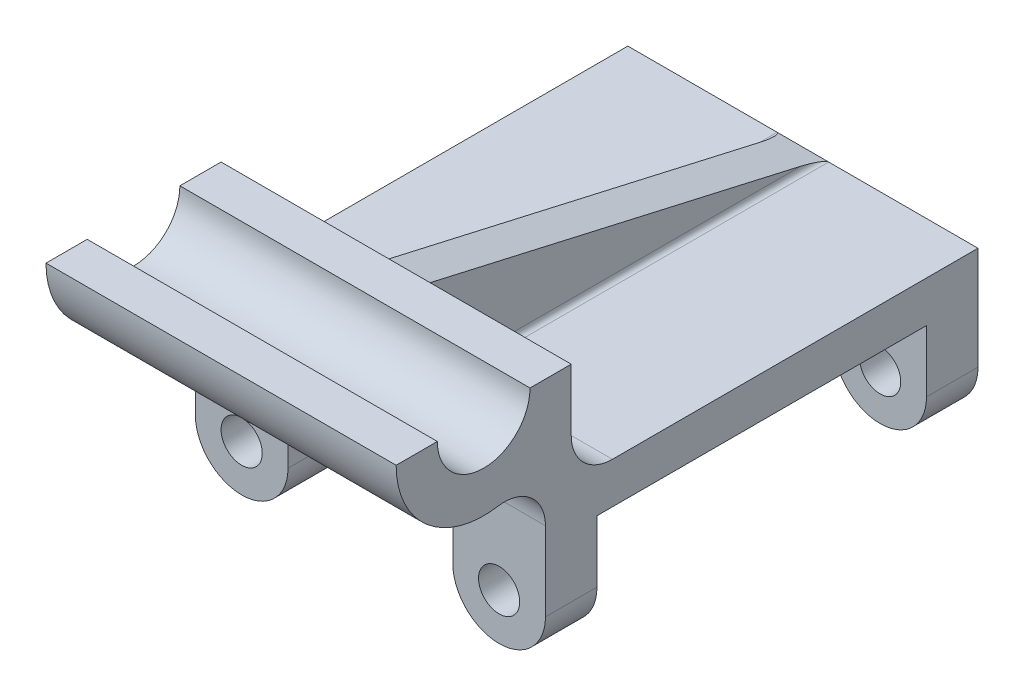
SolidWorks part; units mm, degrees
ref_plane "Front Plane" through (0, 0, 0) normal (0, 0, 1) x (1, 0, 0)
ref_plane "Top Plane" through (0, 0, 0) normal (0, 1, 0) x (1, 0, 0)
ref_plane "Right Plane" through (0, 0, 0) normal (1, 0, 0) x (0, 0, -1)
sketch "Sketch2" plane through (0, 0, 0) normal (1, 0, 0) x (0, 0, -1)
  line L0 (0, 0) -> (133.35, 0)
  line L1 (133.35, 0) -> (133.35, 12.7)
  line L2 (133.35, 12.7) -> (20.6375, 12.7)
  line L7 (0, 0) -> (0, 60.5111) construction
  line L8 (7.9375, 25.4) -> (7.9375, 44.45)
  line L9 (7.9375, 44.45) -> (-4.7625, 44.45)
  line L10 (-33.3375, 44.45) -> (-46.0375, 44.45)
  line L11 (0, 5.2738) -> (0, 0)
  line L12 (-37.3298, 44.45) -> (7.9375, 44.45) construction
  arc A2 (-33.3375, 44.45) -> (-4.7625, 44.45) centre (-19.05, 44.45) ccw
  arc A3 (20.6375, 12.7) -> (7.9375, 25.4) centre (20.6375, 25.4) cw
  arc A4 (-46.0375, 44.45) -> (-14.732, 17.8102) centre (-19.05, 44.45) ccw
  arc A5 (-14.732, 17.8102) -> (0, 5.2738) centre (-12.7, 5.2738) cw
  point P16 (0, 0)
  point P17 (0, 0)
  point P18 (0, 0)
  point P20 (0, 0)
  point P21 (0, 0)
  point P22 (0, 5.2738)
  dimension "D3" = 28.575
  dimension "D7" = 12.7
  dimension "D8" = 44.45
  dimension "D5" = 12.7
  dimension "D6" = 26.9875
  dimension "D1" = 133.35
  dimension "D2" = 12.7
  dimension "D4" = 19.05
  dimension "D9" = 12.7
extrude "Boss-Extrude1" add sketch "Sketch2" along normal mid plane 107.95
sketch "Sketch3" plane through (0, 0, 0) normal (1, 0, 0) x (0, 0, -1)
  line L0 (7.9375, 41.275) -> (133.35, 12.7)
  point P2 (0, 0)
  point P3 (0, 0)
  point P4 (0, 0)
  point P6 (0, 0)
  point P7 (7.9375, 44.45)
  dimension "D1" = 3.175
rib "Rib1" sketch "Sketch3" sketch "Sketch3" thickness 12.7 extrusion direction parallel to sketch draft on no parameters "D1"=12.7
sketch "Sketch4" plane through (0, 0, -133.35) normal (0, 0, -1) x (-1, 0, 0)
  line L0 (-53.975, 0) -> (-53.975, -19.05)
  line L1 (-25.4, -19.05) -> (-25.4, 0)
  line L2 (-53.975, 0) -> (53.975, 0) construction
  line L3 (53.975, 0) -> (53.975, 12.7) construction
  line L4 (0, 0) -> (0, 55.3311) construction
  line L5 (25.4, -19.05) -> (25.4, 0)
  line L6 (53.975, 0) -> (53.975, -19.05)
  arc A0 (-53.975, -19.05) -> (-25.4, -19.05) centre (-39.6875, -19.05) ccw
  circle A1 centre (-39.6875, -19.05) radius 6.35
  circle A2 centre (39.6875, -19.05) radius 6.35
  arc A4 (53.975, -19.05) -> (25.4, -19.05) centre (39.6875, -19.05) cw
  line M6 (-53.975, 0) -> (53.975, 0)
  dimension "D1" = 14.2875
  dimension "D2" = 12.7
  dimension "D3" = 19.05
sketch "Sketch5" plane through (0, 0, 0) normal (0, -1, 0) x (1, 0, 0)
  line L0 (0, -133.35) -> (0, 0) construction
  line L1 (53.975, -133.35) -> (-53.975, -133.35) construction
  line L3 (-53.975, -66.675) -> (53.975, -66.675) construction
  line L4 (53.975, 0) -> (53.975, -133.35) construction
  line L5 (-53.975, 0) -> (-53.975, -133.35) construction
  point P9 (0, -66.675)
  point P10 (0, -66.675)
  point P11 (-53.975, -66.675)
extrude "Boss-Extrude2" add sketch "Sketch4" against normal blind 15.875 from surface contours L0 A0 L1 A1 M6 | A4 L6 L5 A2 M6 region at (39.6875, -0.4391, -133.35) region at (-39.6875, -0.4391, -133.35) starting at face at (0, 8.4667, -133.35)
sketch "Sketch6" plane through (0, 0, 0) normal (0, 0, 1) x (1, 0, 0)
  line L0 (-53.975, 5.2738) -> (-53.975, -19.05)
  line L1 (-25.4, -19.05) -> (-25.4, 0)
  line L2 (25.4, 0) -> (25.4, -19.05)
  line L3 (53.975, -19.05) -> (53.975, 0)
  arc A0 (-53.975, -19.05) -> (-25.4, -19.05) centre (-39.6875, -19.05) ccw
  arc A1 (25.4, -19.05) -> (53.975, -19.05) centre (39.6875, -19.05) ccw
  circle A2 centre (-39.6875, -19.05) radius 6.35
  circle A3 centre (39.6875, -19.05) radius 6.35
  circle A4 centre (-39.6875, -19.05) radius 6.35 construction
  circle A5 centre (39.6875, -19.05) radius 6.35 construction
  line M3 (-53.975, 0) -> (53.975, 0)
extrude "Boss-Extrude3" add sketch "Sketch6" against normal blind 15.875 contours L0 A0 L1 A2 M3 | L2 A1 L3 A3 M3 region at (-39.6875, -0.4391, 0) region at (39.6875, -0.4391, 0)
fillet "Fillet1" radius 3.175 1 edges at (0, 41.275, -7.9375)
fillet "Fillet4" radius 1.5875 3 edges at (-6.35, 12.7, -76.9938) (-6.35, 16.4197, -11.6572) (-6.35, 34.604, -7.9375) type face fillet first side face at (-30.1625, 17.7349, -12.9724) first side face at (-30.1625, 12.7, -76.9938) first side face at (30.1625, 12.7, -76.9938) first side face at (30.1625, 17.7349, -12.9724) first side face at (0, 34.7645, -7.9375) second side face at (-6.35, 26.4516, -35.4195)
fillet "Fillet5" radius 1.5875 3 edges at (6.35, 12.7, -76.9938) (6.35, 16.4197, -11.6572) (6.35, 34.604, -7.9375) type face fillet first side face at (30.1625, 12.7, -76.9938) first side face at (30.1625, 17.7349, -12.9724) first side face at (-0.3969, 34.7645, -7.9375) second side face at (6.35, 26.4516, -35.4195)
